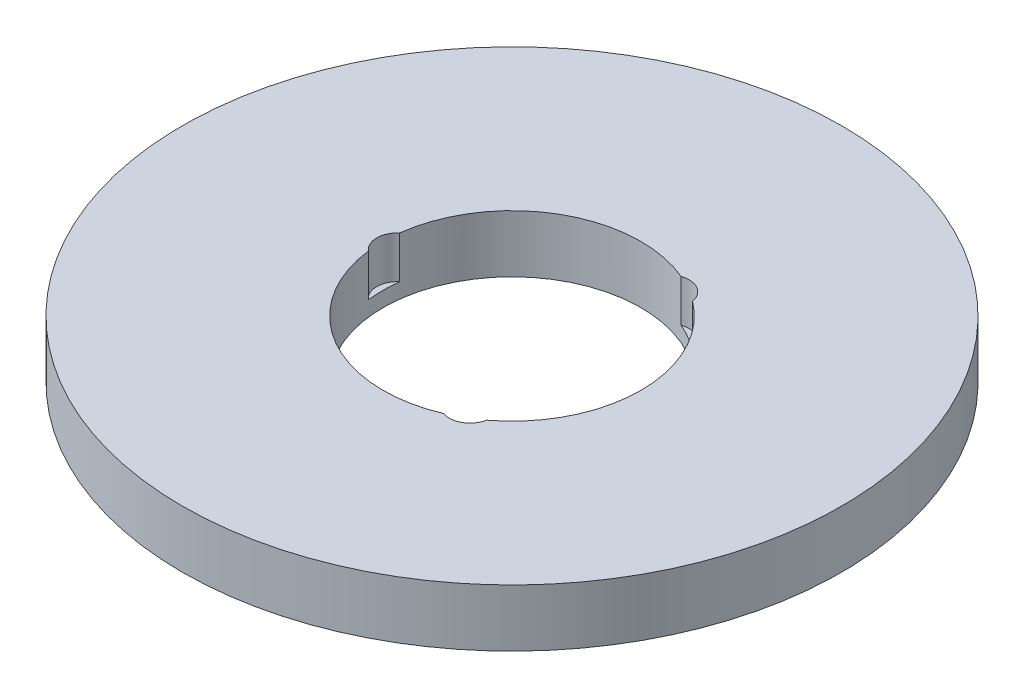
SolidWorks part; units mm, degrees
ref_plane "Front Plane" through (0, 0, 0) normal (0, 0, 1) x (1, 0, 0)
ref_plane "Top Plane" through (0, 0, 0) normal (0, 1, 0) x (1, 0, 0)
ref_plane "Right Plane" through (0, 0, 0) normal (1, 0, 0) x (0, 0, -1)
sketch "Sketch1" plane through (0, 0, 0) normal (0, 1, 0) x (1, 0, 0)
  circle A0 centre (0, 0) radius 57.5
  dimension "FLANGE_OD" = 115
extrude "Boss-Extrude1" add sketch "Sketch1" along normal blind 10
sketch "Sketch2" plane through (0, 0, 0) normal (0, 1, 0) x (1, 0, 0)
  circle A0 centre (0, 0) radius 22.5
  dimension "BORE_D" = 45
extrude "Cut-Extrude1" cut sketch "Sketch2" along normal through all
sketch "Sketch3" plane through (0, 10, 0) normal (0, 1, 0) x (1, 0, 0)
  circle A0 centre (0, 0) radius 20.0009 construction
  circle A1 centre (-20.0009, 0) radius 3.5966
  dimension "BOLT_D" = 7.1932
  dimension "BOLT_PCD" = 40.0019
extrude "Cut-Extrude2" cut sketch "Sketch3" against normal blind 7.3714
pattern_circular "CirPattern1" count 3 over 360 about axis through (0, 0, 0) along (0, 1, 0) of "Cut-Extrude2"
